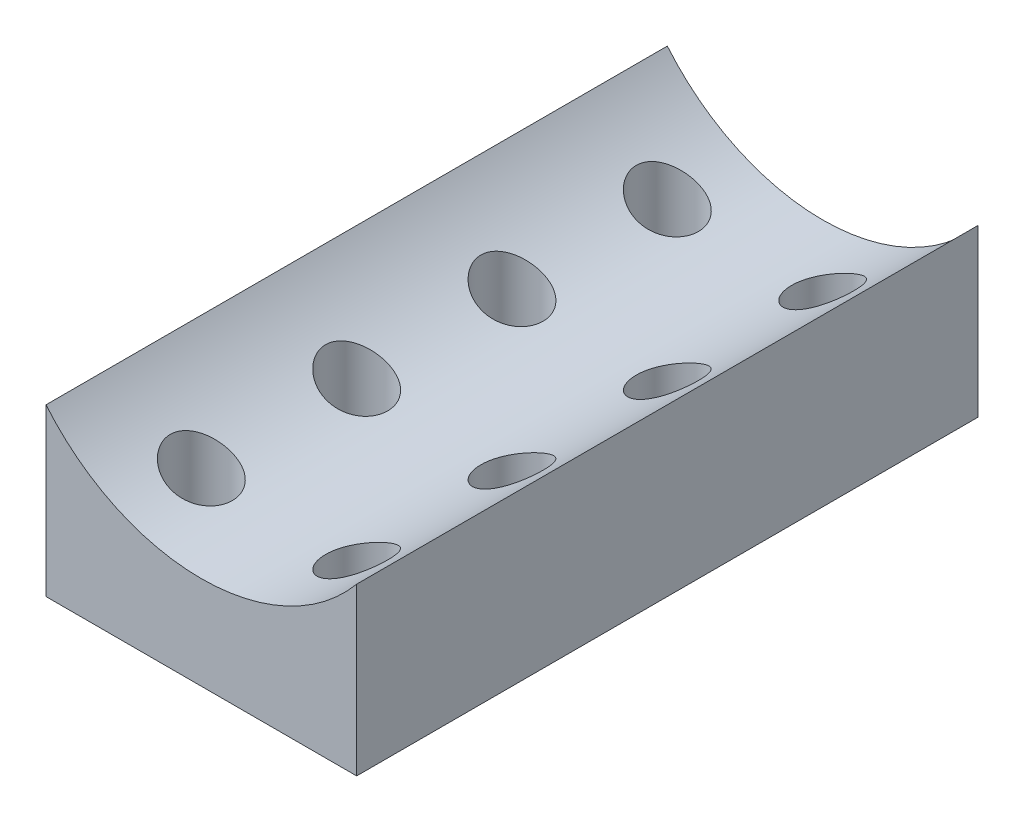
SolidWorks part; units mm, degrees
ref_plane "Front Plane" through (0, 0, 0) normal (0, 0, 1) x (1, 0, 0)
ref_plane "Top Plane" through (0, 0, 0) normal (0, 1, 0) x (1, 0, 0)
ref_plane "Right Plane" through (0, 0, 0) normal (1, 0, 0) x (0, 0, -1)
sketch "Sketch1" plane through (0, 0, 0) normal (0, 0, 1) x (1, 0, 0)
  line L1 (-10, -5.3467) -> (10, -5.3467)
  line L2 (-10, -5.3467) -> (-10, 5.3467)
  line L3 (-10, 5.3467) -> (10, 5.3467) construction
  line L4 (10, -5.3467) -> (10, 5.3467)
  line L5 (-10, -5.3467) -> (10, 5.3467) construction
  line L6 (-10, 5.3467) -> (10, -5.3467) construction
  arc A0 (-10, 5.3467) -> (10, 5.3467) centre (0, 13.6533) ccw
  point P0 (0, 0)
  dimension "D3" = 26
  dimension "D1" = 20
  dimension "D2" = 19
extrude "Boss-Extrude1" add sketch "Sketch1" along normal blind 40
sketch "Sketch2" plane through (0, -5.3467, 0) normal (0, -1, 0) x (1, 0, 0)
  line L0 (-5, 5) -> (5, 5) construction
  line L1 (0, 5) -> (0, 0) construction
  circle A0 centre (5, 5) radius 2
  circle A1 centre (-5, 5) radius 2
  circle A2 centre (-5, 15) radius 2
  circle A3 centre (5, 15) radius 2
  circle A4 centre (-5, 25) radius 2
  circle A5 centre (5, 25) radius 2
  circle A6 centre (-5, 35) radius 2
  circle A7 centre (5, 35) radius 2
  dimension "D2" = 4
  dimension "D1" = 10
  dimension "D3" = 5
  dimension "D4" = 4
extrude "Cut-Extrude1" cut sketch "Sketch2" against normal through all
